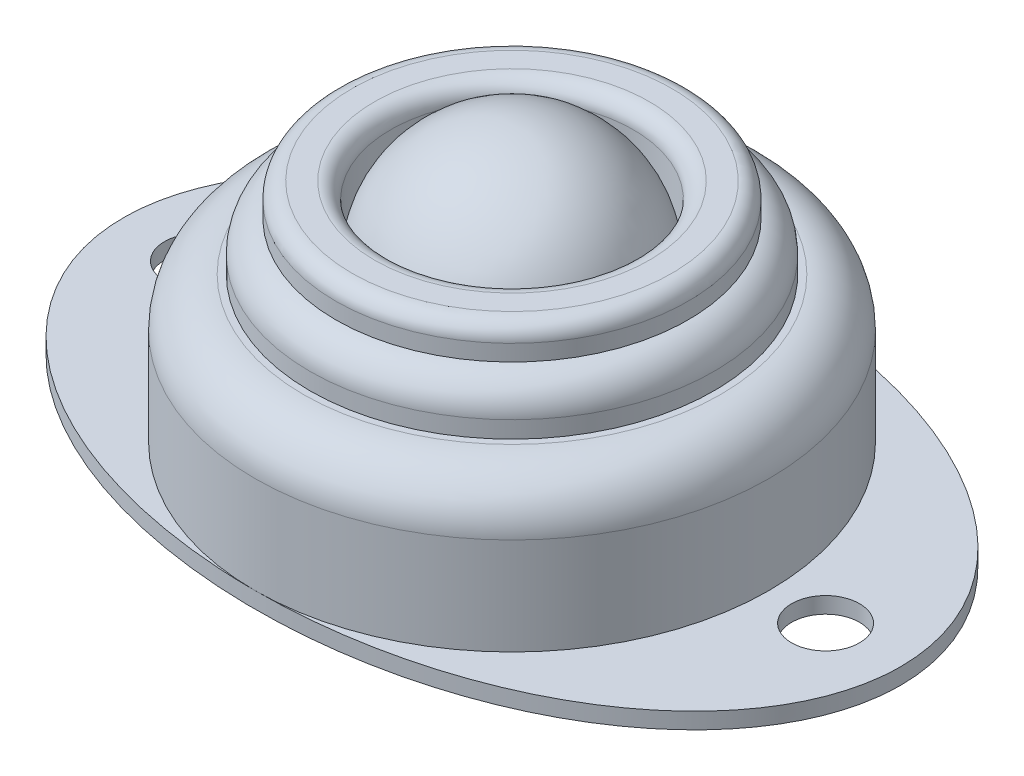
SolidWorks part; units mm, degrees
ref_plane "前视基准面" through (0, 0, 0) normal (0, 0, 1) x (1, 0, 0)
ref_plane "上视基准面" through (0, 0, 0) normal (0, 1, 0) x (1, 0, 0)
ref_plane "右视基准面" through (0, 0, 0) normal (1, 0, 0) x (0, 0, -1)
sketch "草图1" plane through (0, 0, 0) normal (0, 1, 0) x (1, 0, 0)
  line L0 (-24.05, 0) -> (24.05, 0) construction
  line L1 (0, 15.9) -> (0, -15.9) construction
  circle A0 centre (0, 0) radius 15.9
  circle A1 centre (-19.4, 0) radius 2.1
  circle A2 centre (19.4, 0) radius 2.1
  ellipse E0 centre (0, 0) end of major axis (24.05, 0) minor radius 15.9
  dimension "D1" = 31.8
  dimension "D3" = 38.8
  dimension "D4" = 4.2
  dimension "D2" = 24.05
extrude "凸台-拉伸1" add sketch "草图1" along normal blind 1 contours A0 E0 A1 | A0 | A0 E0 A2 region at (0, 0, 0) region at (16.7768, 0, 0) region at (-16.7768, 0, 0)
extrude "凸台-拉伸2" add sketch "草图1<3>" along normal blind 15 contours A0
sketch "草图1<3>" plane through (0, 0, 0) normal (0, 1, 0) x (1, 0, 0) same geometry as "草图1"
sketch "草图2" plane through (0, 15, 0) normal (0, 1, 0) x (1, 0, 0)
  circle A0 centre (0, 0) radius 7.5
  dimension "D1" = 15
extrude "切除-拉伸2" cut sketch "草图2" against normal blind 12 contours A0
sketch "草图5" plane through (0, 3, 0) normal (0, 1, 0) x (1, 0, 0)
  circle A0 centre (0, 0) radius 7.5
extrude "凸台-拉伸4" add sketch "草图5" along normal blind 15 separate body
fillet "圆角4" radius 7.5 2 edges at (0, 3, 7.5) (0, 18, 7.5)
sketch "草图6" plane through (0, 15, 0) normal (0, 1, 0) x (1, 0, 0)
  circle A0 centre (0, 0) radius 12.5
  circle A1 centre (0, 0) radius 15.9
  dimension "D1" = 25
extrude "切除-拉伸3" cut sketch "草图6" against normal blind 5
sketch "草图7" plane through (0, 15, 0) normal (0, 1, 0) x (1, 0, 0)
  circle A0 centre (0, 0) radius 12.5
  circle A1 centre (0, 0) radius 10.9
  circle A2 centre (0, 0) radius 15.9 construction
  dimension "D1" = 5
extrude "切除-拉伸4" cut sketch "草图7" against normal blind 2
fillet "圆角5" radius 1 2 edges at (0, 15, 10.9) (0, 15, 7.5)
fillet "圆角8" radius 3 1 edges at (0, 10, 15.9)
fillet "圆角9" radius 2 1 edges at (0, 13, 12.5)
